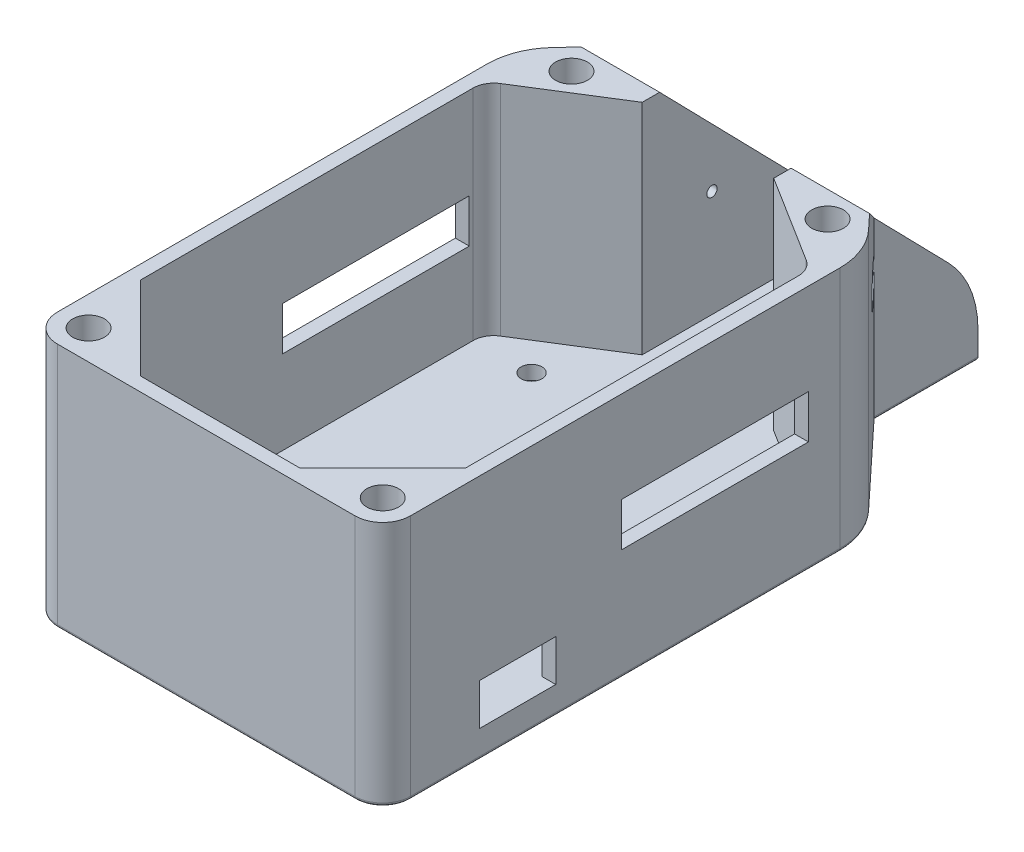
SolidWorks part; units mm, degrees
ref_plane "Front Plane" through (0, 0, 0) normal (0, 0, 1) x (1, 0, 0)
ref_plane "Top Plane" through (0, 0, 0) normal (0, 1, 0) x (1, 0, 0)
ref_plane "Right Plane" through (0, 0, 0) normal (1, 0, 0) x (0, 0, -1)
sketch "Sketch1" plane through (0, -17.9455, 0) normal (0, -1, 0) x (1, 0, 0)
  line L0 (-7.9447, 39.1511) -> (-7.9447, 84.1511) construction
  line L1 (40.0553, 4.1511) -> (-10.9447, 4.1511)
  line L2 (40.0553, 4.1511) -> (40.0553, 104.1511)
  line L3 (40.0553, 104.1511) -> (-10.9447, 104.1511)
  line L4 (-10.9447, 4.1511) -> (-10.9447, 104.1511)
  line L5 (37.0553, 84.1511) -> (37.0553, 39.1511) construction
  line L6 (37.0553, 39.1511) -> (-7.9447, 39.1511) construction
  line L7 (-7.9447, 84.1511) -> (37.0553, 84.1511) construction
  line L8 (40.0553, 34.1511) -> (26.0553, 19.1511)
  line L9 (26.0553, 19.1511) -> (26.0553, 4.1511)
  line L10 (3.0553, 4.1511) -> (3.0553, 19.1511)
  line L11 (3.0553, 19.1511) -> (-10.9447, 34.1511)
  line L12 (5.0553, 27.2658) -> (5.0553, 33.1063) construction
  line L13 (24.0553, 27.2658) -> (24.0553, 33.1063) construction
  circle M7 centre (-0.6947, 41.9011) radius 1.25
  arc M8 (0.5553, 39.736) -> (1.8053, 41.9011) centre (-0.6947, 41.9011) ccw
  arc M9 (1.8053, 41.9011) -> (0.5553, 44.0662) centre (-0.6947, 41.9011) ccw
  arc M10 (0.5553, 44.0662) -> (-1.9447, 44.0662) centre (-0.6947, 41.9011) ccw
  arc M11 (-1.9447, 44.0662) -> (-3.1947, 41.9011) centre (-0.6947, 41.9011) ccw
  arc M12 (-3.1947, 41.9011) -> (-1.9447, 39.736) centre (-0.6947, 41.9011) ccw
  arc M13 (-1.9447, 39.736) -> (0.5553, 39.736) centre (-0.6947, 41.9011) ccw
  dimension "D1" = 3
  dimension "D2" = 3
  dimension "D3" = 35
  dimension "D4" = 20
  dimension "D5" = 15
  dimension "D6" = 15
  dimension "D7" = 15
  dimension "D8" = 15
  dimension "D9" = 2
  dimension "D10" = 2
extrude "Boss-Extrude1" add sketch "Sketch1" along normal blind 4 contours L11 L10 L1 L9 L8 L2 L3 L4 M8 M13 M12 M11 M10 M9 | M13 M8 M9 M10 M11 M12 M7 | M7 region at (14.6226, -17.9455, 59.6317) region at (-0.6947, -17.9455, 41.9011) region at (-0.6947, -17.9455, 39.4718)
sketch "Sketch2" plane through (0, -17.9455, 0) normal (0, 1, 0) x (1, 0, 0)
  line L8 (5.0553, -19.9394) -> (5.0553, -31.6642)
  line L9 (5.0553, -31.6642) -> (-8.9447, -46.6642) construction
  line L10 (24.0553, -19.9394) -> (24.0553, -31.6642)
  line L11 (24.0553, -31.6642) -> (38.0553, -46.6642) construction
  line L12 (5.0553, -31.6642) -> (-8.9447, -40.4394)
  line L13 (24.0553, -31.6642) -> (38.0553, -40.4394)
  line L16 (5.0553, -19.9394) -> (-8.9447, -34.9394)
  line L17 (-8.9447, -34.9394) -> (-8.9447, -102.1511)
  line L18 (-8.9447, -102.1511) -> (38.0553, -102.1511)
  line L19 (38.0553, -102.1511) -> (38.0553, -34.9394)
  line L20 (38.0553, -34.9394) -> (24.0553, -19.9394)
  line L21 (24.0553, -19.9394) -> (24.0553, -6.1511)
  line L22 (24.0553, -6.1511) -> (5.0553, -6.1511)
  line L23 (5.0553, -6.1511) -> (5.0553, -19.9394)
  line L24 (5.0553, -19.9394) -> (-8.9447, -34.9394)
  line L25 (-8.9447, -34.9394) -> (-8.9447, -102.1511)
  line L26 (-8.9447, -102.1511) -> (38.0553, -102.1511)
  line L27 (38.0553, -102.1511) -> (38.0553, -34.9394)
  line L28 (38.0553, -34.9394) -> (24.0553, -19.9394)
  line L29 (24.0553, -19.9394) -> (24.0553, -6.1511)
  line L30 (24.0553, -6.1511) -> (5.0553, -6.1511)
  line L31 (5.0553, -6.1511) -> (5.0553, -19.9394)
  line M9 (3.0553, -19.1511) -> (-10.9447, -34.1511)
  line M10 (-10.9447, -34.1511) -> (-10.9447, -104.1511)
  line M11 (-10.9447, -104.1511) -> (40.0553, -104.1511)
  line M12 (40.0553, -104.1511) -> (40.0553, -34.1511)
  line M13 (40.0553, -34.1511) -> (26.0553, -19.1511)
  line M14 (26.0553, -19.1511) -> (26.0553, -4.1511)
  line M15 (26.0553, -4.1511) -> (3.0553, -4.1511)
  line M16 (3.0553, -4.1511) -> (3.0553, -19.1511)
  dimension "D2" = 8
  dimension "D3" = 8
  dimension "D4" = 5.5
  dimension "D5" = 5.5
  dimension "D1" = 2
extrude "Boss-Extrude2" add sketch "Sketch2" along normal up to surface (31.6 mm away) contours L31 L30 L29 L28 L27 L26 L25 L24 M16 M9 M10 M11 M12 M13 M14 M15 | L24 L25 L9 L8 | L27 L28 L10 L11 region at (-1.1015, -17.9455, 31.0296) region at (30.2121, -17.9455, 31.0296) region at (4.1779, -17.9455, 11.6511)
sketch "Sketch3" plane through (-10.9447, 0, 0) normal (-1, 0, 0) x (0, 0, 1)
  line L0 (29.1511, 13.6545) -> (4.1511, -11.9455)
  line L1 (4.1511, -21.9455) -> (4.1511, 13.6545) construction
  line L3 (34.1511, 13.6545) -> (19.1511, 13.6545) construction
  line L4 (29.1511, 13.6545) -> (4.1511, 13.6545)
  line L5 (19.1511, 13.6545) -> (4.1511, 13.6545) construction
  line L6 (4.1511, -11.9455) -> (4.1511, 13.6545)
  line L7 (4.1511, -21.9455) -> (19.1511, -21.9455) construction
  dimension "D1" = 5
  dimension "D2" = 10
extrude "Cut-Extrude1" cut sketch "Sketch3" against normal through all
fillet "Fillet1" radius 15 1 edges at (14.5553, -11.9455, 4.1511)
fillet "Fillet2" radius 3 2 edges at (5.0553, -14.2585, 6.1511) (24.0553, -14.2585, 6.1511)
fillet "Fillet3" radius 3 2 edges at (-8.9447, -2.1455, 40.4394) (38.0553, -2.1455, 40.4394)
sketch "Sketch4" plane through (0, -21.9455, 0) normal (0, -1, 0) x (1, 0, 0)
  circle A0 centre (29.8053, 72.4011) radius 1.25 construction
  circle A1 centre (29.8053, 41.9011) radius 1.25 construction
  circle A2 centre (-0.6947, 41.9011) radius 1.25 construction
  circle A3 centre (-0.6947, 72.4011) radius 1.25 construction
  circle A4 centre (29.8053, 72.4011) radius 1.25 construction
  circle A5 centre (29.8053, 41.9011) radius 1.25 construction
  circle A6 centre (-0.6947, 41.9011) radius 1.25 construction
  circle A7 centre (-0.6947, 72.4011) radius 1.25 construction
  circle A8 centre (-0.6947, 41.9011) radius 3.25
  circle A9 centre (-0.6947, 72.4011) radius 3.25
  circle A10 centre (29.8053, 72.4011) radius 3.25
  circle A11 centre (29.8053, 41.9011) radius 3.25
  dimension "D1" = 6.5
  dimension "D2" = 6.5
  dimension "D3" = 6.5
  dimension "D4" = 6.5
extrude "Cut-Extrude2" cut sketch "Sketch4" against normal blind 2
sketch "Sketch5" plane through (0, -19.9455, 0) normal (0, -1, 0) x (1, 0, 0)
  circle A0 centre (-0.6947, 41.9011) radius 1.5
  circle A1 centre (-0.6947, 72.4011) radius 1.5
  circle A2 centre (29.8053, 72.4011) radius 1.5
  circle A3 centre (29.8053, 41.9011) radius 1.5
  dimension "D1" = 3
  dimension "D2" = 3
  dimension "D3" = 3
  dimension "D4" = 3
extrude "Cut-Extrude3" cut sketch "Sketch5" against normal through all
chamfer "Chamfer1" distance 12 angle 45 2 edges at (-8.9447, -2.1455, 102.1511) (38.0553, -2.1455, 102.1511)
sketch "Sketch6" plane through (0, 13.6545, 0) normal (0, 1, 0) x (1, 0, 0)
  line L1 (40.0553, -104.1511) -> (-10.9447, -104.1511) construction
  line L2 (40.0553, -34.1511) -> (40.0553, -104.1511) construction
  line L3 (-10.9447, -104.1511) -> (-10.9447, -34.1511) construction
  circle A0 centre (33.0553, -32.8815) radius 2.3
  circle A1 centre (-3.9447, -32.8815) radius 2.3
  circle A2 centre (35.8053, -99.9011) radius 2.3
  circle A3 centre (-6.6947, -99.9011) radius 2.3
  point P16 (39.4466, -97.7414)
  point P21 (-5.8208, -104.1511)
  dimension "D1" = 4.6
  dimension "D4" = 4.6
  dimension "D7" = 4.6
  dimension "D8" = 4.6
  dimension "D2" = 7
  dimension "D3" = 4.4
  dimension "D5" = 7
  dimension "D6" = 4.4
  dimension "D9" = 4.25
  dimension "D10" = 4.25
  dimension "D11" = 4.25
  dimension "D12" = 4.25
extrude "Cut-Extrude4" cut sketch "Sketch6" against normal blind 7
fillet "Fillet4" radius 10 2 edges at (40.0553, -4.1455, 34.1511) (-10.9447, -4.1455, 34.1511)
fillet "Fillet5" radius 4 2 edges at (40.0553, -4.1455, 104.1511) (-10.9447, -4.1455, 104.1511)
sketch "Sketch8" plane through (3.0553, 0, 0) normal (-1, 0, 0) x (0, 0, 1)
  circle A1 centre (21.5861, -2.526) radius 0.75
  circle A2 centre (21.5861, -2.526) radius 0.75
  dimension "D1" = 0
extrude "Cut-Extrude5" cut sketch "Sketch8" against normal through all and the other way through all
sketch "Sketch9" plane through (3.0553, 0, 0) normal (-1, 0, 0) x (0, 0, 1)
  circle A0 centre (21.5861, -2.526) radius 0.75 construction
  circle A1 centre (21.5861, -2.526) radius 0.75 construction
  circle A2 centre (21.5861, -2.526) radius 2.5
  dimension "D1" = 5
extrude "Cut-Extrude6" cut sketch "Sketch9" along normal through all
extrude "Cut-Extrude7" cut sketch "Sketch9<2>" against normal through all from surface starting at face at (26.0553, -13.1376, 10.7995)
sketch "Sketch9<2>" plane through (3.0553, 0, 0) normal (-1, 0, 0) x (0, 0, 1) same geometry as "Sketch9"
sketch "Sketch10" plane through (-10.9447, 0, 0) normal (-1, 0, 0) x (0, 0, 1)
  line L1 (42.6511, -5.8455) -> (69.6511, -5.8455)
  line L2 (42.6511, -5.8455) -> (42.6511, 0.4545)
  line L3 (42.6511, 0.4545) -> (69.6511, 0.4545)
  line L4 (69.6511, -5.8455) -> (69.6511, 0.4545)
  line L5 (66.2511, -1.0455) -> (67.1511, -1.0455) construction
  line L6 (67.6511, -4.3455) -> (69.6511, -4.3455) construction
  line L7 (45.1511, -4.3455) -> (45.1511, -1.5455) construction
  line L8 (67.1511, -4.3455) -> (67.1511, -1.5455) construction
  dimension "D1" = 1.5
  dimension "D2" = 1.5
  dimension "D3" = 2.5
  dimension "D4" = 2.5
extrude "Cut-Extrude8" cut sketch "Sketch10" against normal through all
fillet "Fillet6" radius 0.5 16 edges at (39.3587, -21.9455, 34.4257) (31.7106, -21.9455, 25.2103) (26.0553, -21.9455, 11.6511) (14.5553, -21.9455, 4.1511) (3.0553, -21.9455, 11.6511) (-2.6, -21.9455, 25.2103) (-10.2481, -21.9455, 34.4257) (-10.9447, -21.9455, 69.1219) (-9.7731, -21.9455, 102.9795) (14.5553, -21.9455, 104.1511) (38.8837, -21.9455, 102.9795) (40.0553, -21.9455, 69.1219) (-0.6947, -21.9455, 38.6511) (-0.6947, -21.9455, 69.1511) (29.8053, -21.9455, 69.1511) (29.8053, -21.9455, 38.6511)
sketch "Sketch11" plane through (38.0553, 0, 0) normal (-1, 0, 0) x (0, 0, 1)
  line L0 (90.1511, -17.9455) -> (42.0996, -17.9455) construction
  line L1 (90.1511, -17.9455) -> (79.1511, -17.9455)
  line L2 (90.1511, -17.9455) -> (90.1511, -11.9455)
  line L3 (90.1511, -11.9455) -> (79.1511, -11.9455)
  line L4 (79.1511, -17.9455) -> (79.1511, -11.9455)
  dimension "D1" = 6
  dimension "D2" = 11
extrude "Cut-Extrude9" cut sketch "Sketch11" against normal through all
